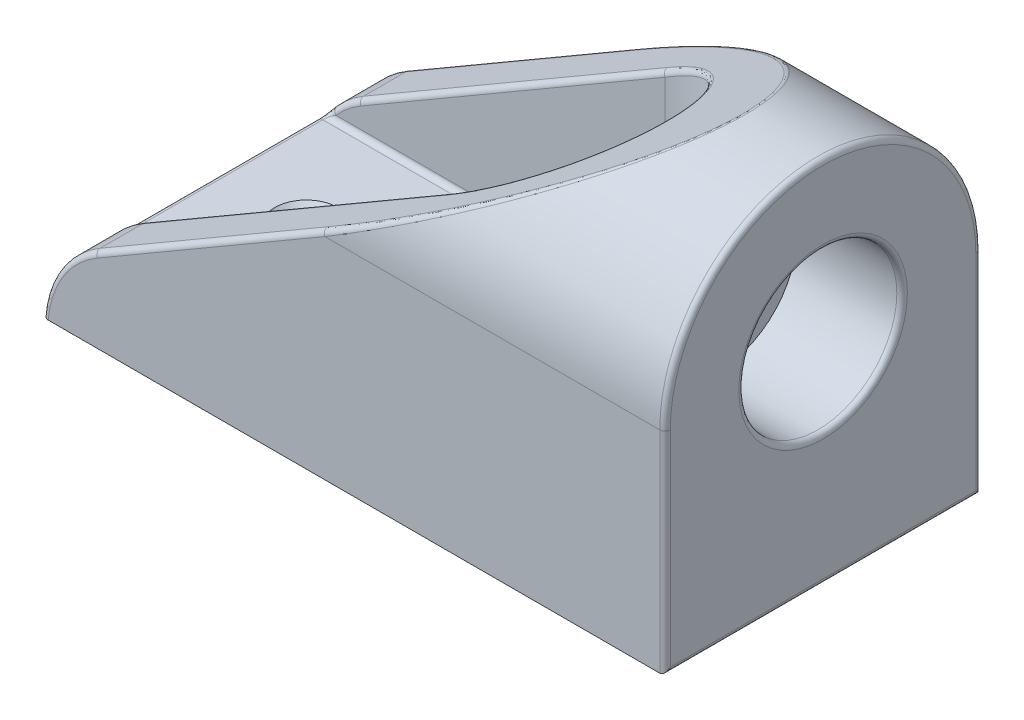
SolidWorks part; units mm, degrees
material "Nylon 101"
ref_plane "Front Plane" through (0, 0, 0) normal (0, 0, 1) x (1, 0, 0)
ref_plane "Top Plane" through (0, 0, 0) normal (0, 1, 0) x (1, 0, 0)
ref_plane "Right Plane" through (0, 0, 0) normal (1, 0, 0) x (0, 0, -1)
sketch "Sketch2" plane through (0, 0, 0) normal (1, 0, 0) x (0, 0, -1)
  line L1 (-19.05, 0) -> (19.05, 0)
  line L2 (-19.05, 0) -> (-19.05, 25.4)
  line L3 (-19.05, 25.4) -> (19.05, 25.4)
  line L4 (19.05, 0) -> (19.05, 25.4)
  arc A0 (-19.05, 25.4) -> (19.05, 25.4) centre (0, 25.4) cw
  circle A1 centre (0, 25.4) radius 9.525
  point P4 (0, 0)
  dimension "D1" = 19.05
  dimension "D2" = 38.1
  dimension "D3" = 25.4
extrude "Boss-Extrude1" add sketch "Sketch2" against normal blind 75 contours A1 L3 L2 L1 L4 | A1 L3 A0 | L3 A1 | L3 A1 | L3 | L3 region at (0, 11.2049, 0) region at (0, 44.024, 0) region at (0, 29.4425, 0) region at (0, 21.3575, 0)
extrude "Cut-Extrude4" cut sketch "Sketch2<4>" against normal blind 12.7 contours L3 A1 | L3 A1 region at (0, 29.4425, 0) region at (0, 21.3575, 0)
sketch "Sketch2<4>" plane through (0, 0, 0) normal (1, 0, 0) x (0, 0, -1) same geometry as "Sketch2"
hole_wizard "CBORE for 3/8 Socket Head Cap Screw1" positions "Sketch9" profile "Sketch10" counterbore size "3/8" standard "ANSI Inch" end condition through all
sketch "Sketch9" plane through (-12.7, 0, 0) normal (1, 0, 0) x (0, 0, -1)
  point P0 (0, 25.4)
sketch "Sketch10" plane through (-12.7, 25.4, 0) normal (0, 1, 0) x (0, 0, -1)
  line L0 (0, 0) -> (0, 62.3)
  line L1 (0, 62.3) -> (4.7879, 62.3)
  line L3 (4.7879, 62.3) -> (4.7879, 1.5875)
  line L4 (4.7879, 1.5875) -> (6.985, 1.5875)
  line L5 (6.985, 1.5875) -> (6.985, 0)
  line L7 (6.985, 0) -> (0, 0)
  line L11 (0, -6.35) -> (0, 107.95) construction
  dimension "Thru Hole Dia." = 9.5758
  dimension "Thru Hole Depth" = 62.3
  dimension "C'Bore Dia." = 13.97
  dimension "C'Bore Depth" = 1.5875
sketch "Sketch3" plane through (0, 0, 0) normal (0, 0, 1) x (1, 0, 0)
  line L0 (-75, 6.35) -> (-9.525, 44.45)
  line L13 (-9.525, 44.45) -> (-75, 44.45)
  line L15 (-75, 44.45) -> (-75, 6.35)
  line L16 (0, 25.4) -> (0, 44.45) construction
  line L18 (0, 44.45) -> (-75, 44.45) construction
  line L19 (-75, 0) -> (-75, 25.4) construction
  line L20 (-75, 0) -> (0, 0) construction
  dimension "D1" = 9.525
  dimension "D2" = 6.35
extrude "Cut-Extrude1" cut sketch "Sketch3" against normal through all both and the other way through all
sketch "Sketch4" plane through (0, 0, 0) normal (0, 1, 0) x (1, 0, 0)
  line L0 (-75, 12.7) -> (-31.75, 12.7)
  line L1 (-31.75, -12.7) -> (-75, -12.7)
  line L6 (-12.7, -12.7) -> (-12.7, 12.7) construction
  line L7 (-75, 19.05) -> (-75, -19.05) construction
  line L8 (-75, 19.05) -> (-42.2625, 19.05) construction
  line L13 (-75, 12.7) -> (-75, -12.7)
  line L14 (-12.7, -9.525) -> (-12.7, 9.525) construction
  arc A0 (-31.75, 12.7) -> (-31.75, -12.7) centre (-31.75, 0) cw
  dimension "D1" = 6.35
  dimension "D2" = 6.35
extrude "Cut-Extrude5" cut sketch "Sketch4" along normal through all from offset 6.35
sketch "Sketch5" plane through (0, 0, 0) normal (0, 1, 0) x (1, 0, 0)
  line L0 (-75, 0) -> (0, 0) construction
  line L1 (-75, 12.7) -> (-75, -12.7) construction
  line L2 (0, -19.05) -> (0, 19.05) construction
  arc A0 (-31.75, -12.7) -> (-31.75, 12.7) centre (-31.75, 0) ccw construction
  point P6 (-62.3, 0)
  point P7 (-31.75, 0)
  dimension "D1" = 12.7
hole_wizard "1/4 (0.25) Diameter Hole1" positions "Sketch6" profile "Sketch8" hole size "1/4" standard "ANSI Inch"
sketch "Sketch6" plane through (0, 6.35, 0) normal (0, 1, 0) x (1, 0, 0)
  point P0 (-62.3, 0)
  point P3 (-31.75, 0)
sketch "Sketch8" plane through (-62.3, 6.35, 0) normal (1, 0, 0) x (0, 0, 1)
  line L0 (0, 0) -> (0, 10.7977)
  line L1 (0, 10.7977) -> (3.175, 8.89)
  line L2 (3.175, 8.89) -> (3.175, 0.635)
  line L3 (3.175, 0.635) -> (3.81, 0)
  line L5 (3.81, 0) -> (0, 0)
  line L6 (-3.175, 0.635) -> (-3.81, 0) construction
  line L10 (0, 10.7977) -> (-3.175, 8.89) construction
  line L11 (0, -6.35) -> (0, 107.95) construction
  dimension "Hole Dia." = 6.35
  dimension "Hole Depth" = 8.89
  dimension "Near C'Sink Dia." = 7.62
  dimension "Near C'Sink Angle" = 90
  dimension "Drill Angle" = 118
fillet "Fillet1" radius 12.7 1 edges at (-75, 6.35, 15.875) tangent propagation no
fillet "Fillet2" radius 0.635 19 edges at (0, 12.7, -19.05) (0, 0, 0) (0, 12.7, 19.05) (0, 44.45, 0) (0, 25.4, -9.525) (-9.525, 44.45, 0) (-55.4937, 17.7007, 19.05) (-50.2375, 20.7594, 12.7) (-19.05, 38.9074, 0) (-50.2375, 20.7594, -12.7) (-55.4937, 17.7007, -19.05) (-52.231, 6.35, 12.7) (-19.05, 6.35, 0) (-52.231, 6.35, -12.7) (-72.712, 6.35, 0) (-73.0954, 5.7743, 19.05) (-73.0954, 5.7743, -19.05) (-70.915, 8.3904, 12.7) (-70.915, 8.3904, -12.7)
